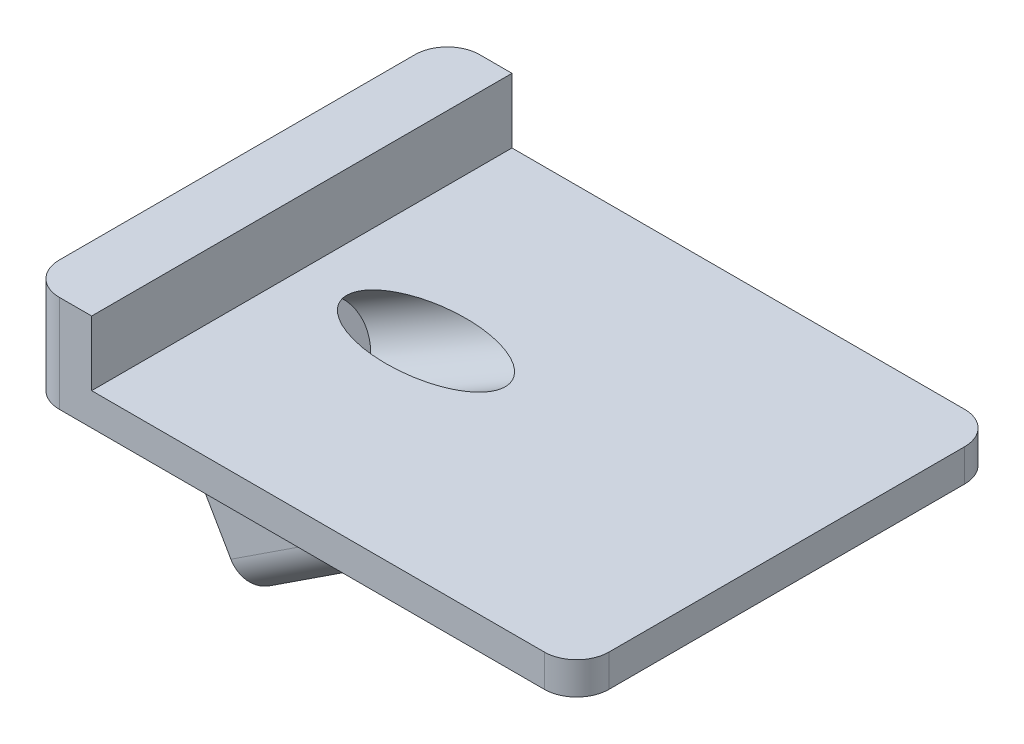
SolidWorks part; units mm, degrees
ref_plane "Ebene vorne" through (0, 0, 0) normal (0, 0, 1) x (1, 0, 0)
ref_plane "Ebene oben" through (0, 0, 0) normal (0, 1, 0) x (1, 0, 0)
ref_plane "Ebene rechts" through (0, 0, 0) normal (1, 0, 0) x (0, 0, -1)
sketch "Skizze2" plane through (0, 0, 0) normal (0, 1, 0) x (1, 0, 0)
  line L0 (-32.5, 32.5) -> (-32.5, -32.5) construction
  line L1 (42.5, 32.5) -> (-42.5, 32.5)
  line L2 (42.5, 32.5) -> (42.5, -32.5)
  line L3 (42.5, -32.5) -> (-42.5, -32.5)
  line L4 (-42.5, 32.5) -> (-42.5, -32.5)
  line L5 (42.5, 32.5) -> (-42.5, -32.5) construction
  line L6 (42.5, -32.5) -> (-42.5, 32.5) construction
  point P0 (0, 0)
  dimension "D1" = 65
  dimension "D2" = 85
  dimension "D3" = 10
extrude "Aufsatz-Linear austragen1" add sketch "Skizze2" along normal blind 5
sketch "Skizze3" plane through (0, 5, 0) normal (0, 1, 0) x (1, 0, 0)
  line L0 (-42.5, -32.5) -> (42.5, -32.5) construction
  line L1 (-42.5, 32.5) -> (-32.5, 32.5)
  line L2 (-42.5, 32.5) -> (-42.5, -32.5)
  line L3 (-42.5, -32.5) -> (-32.5, -32.5)
  line L4 (-32.5, 32.5) -> (-32.5, -32.5)
  dimension "D1" = 10
extrude "Aufsatz-Linear austragen2" add sketch "Skizze3" along normal blind 10
sketch "Skizze4" plane through (0, 0, 0) normal (0, 0, 1) x (1, 0, 0)
  line L0 (17.769, 0) -> (-25.9637, -28.6417)
  line L1 (-42.5, 0) -> (42.5, 0) construction
  line L2 (-25.9637, -28.6417) -> (-42.5, 0)
  line L9 (-42.5, 0) -> (42.5, 0)
  line L10 (42.5, 0) -> (42.5, 5)
  line L11 (42.5, 5) -> (-32.5, 5)
  line L12 (-32.5, 5) -> (-32.5, 15)
  line L13 (-32.5, 15) -> (-42.5, 15)
  line L14 (-42.5, 15) -> (-42.5, 0)
  line L15 (17.769, 0) -> (42.5, 0)
  line L16 (42.5, 0) -> (42.5, 5)
  line L17 (42.5, 5) -> (-32.5, 5)
  line L18 (-32.5, 5) -> (-32.5, 15)
  line L19 (-32.5, 15) -> (-42.5, 15)
  line L20 (-42.5, 15) -> (-42.5, 0)
  point P6 (17.769, 0)
  dimension "D1" = 60
  dimension "D2" = 0
extrude "Aufsatz-Linear austragen3" add sketch "Skizze4" along normal blind 15 and the other way blind 15
hole_wizard "Durchgangsloch für M61" positions "Skizze5" profile "Skizze6" hole size "M6" standard "DIN" end condition through all
sketch "Skizze5" plane through (-31.875, -18.403, 0) normal (-0.866, -0.5, 0) x (0, 0, 1)
  point P0 (0, 10.9797)
sketch "Skizze6" plane through (-37.3648, -8.8944, 0) normal (0, 0, 1) x (0.5, -0.866, 0)
  line L0 (0, 0) -> (0, 81.1122)
  line L1 (0, 81.1122) -> (3.3, 81.1122)
  line L2 (3.3, 81.1122) -> (3.3, 0)
  line L5 (3.3, 0) -> (0, 0)
  line L11 (0, -6.35) -> (0, 107.95) construction
  dimension "Bohrerdurchmesser" = 6.6
  dimension "Bohrungstiefe" = 81.1122
ref_plane "Ebene1" through (2.766, 1.597, 0) normal (-0.866, -0.5, 0) x (0, 0, 1)
sketch "Skizze7" plane through (2.766, 1.597, 0) normal (-0.866, -0.5, 0) x (0, 0, 1)
  circle A0 centre (0, 10.9797) radius 6.1263
extrude "Schnitt-Linear austragen1" cut sketch "Skizze7" along normal blind 30
sketch "Skizze8" plane through (-31.875, -18.403, 0) normal (-0.866, -0.5, 0) x (0, 0, 1)
  line L1 (-3, -7.953) -> (3, -7.953)
  line L2 (-3, -7.953) -> (-3, 2.047)
  line L3 (-3, 2.047) -> (3, 2.047)
  line L4 (3, -7.953) -> (3, 2.047)
  line L5 (-3, -7.953) -> (3, 2.047) construction
  line L6 (-3, 2.047) -> (3, -7.953) construction
  point P0 (0, -2.953)
  dimension "D1" = 10
  dimension "D2" = 6
extrude "Aufsatz-Linear austragen4" add sketch "Skizze8" along normal blind 3
fillet "Verrundung1" radius 2 2 edges at (-32.8985, -16.6303, 0) (-27.8985, -25.2906, 0)
fillet "Verrundung2" radius 10 2 edges at (-12.3655, 0, -15) (-12.3655, 0, 15)
fillet "Verrundung3" radius 5 4 edges at (-42.5, 7.5, -32.5) (-42.5, 7.5, 32.5) (42.5, 2.5, -32.5) (42.5, 2.5, 32.5)
fillet "Verrundung4" radius 5 4 edges at (13.2969, -2.9289, 17.9289) (13.2969, -2.9289, -17.9289) (-11.7318, -19.3209, 15) (-11.7318, -19.3209, -15)
